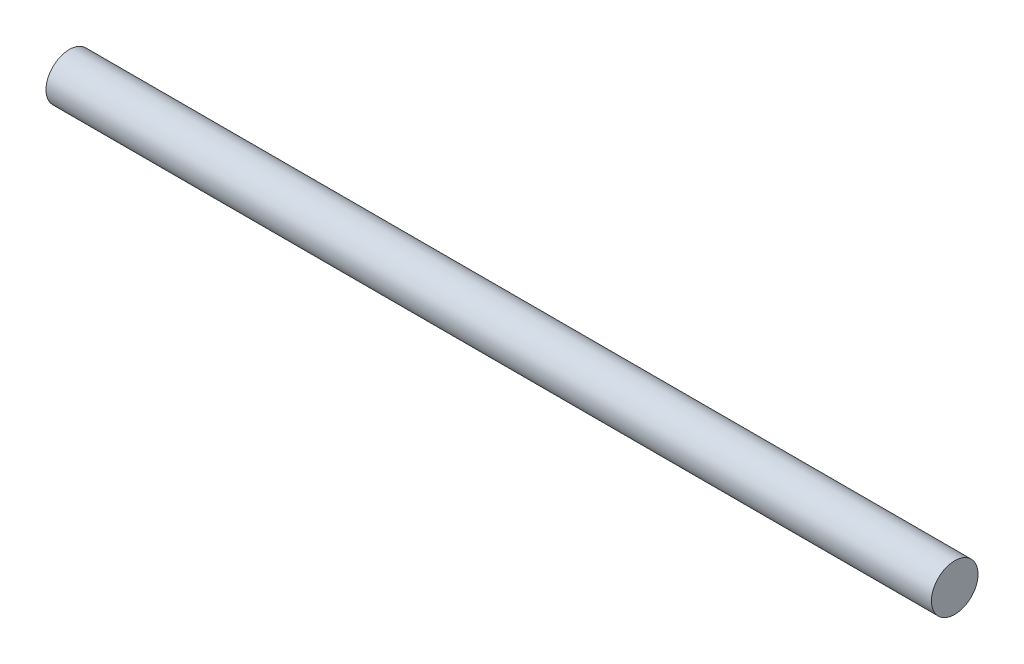
SolidWorks part; units mm, degrees
ref_plane "Front Plane" through (0, 0, 0) normal (0, 0, 1) x (1, 0, 0)
ref_plane "Top Plane" through (0, 0, 0) normal (0, 1, 0) x (1, 0, 0)
ref_plane "Right Plane" through (0, 0, 0) normal (1, 0, 0) x (0, 0, -1)
sketch "Sketch1" plane through (0, 0, 0) normal (1, 0, 0) x (0, 0, -1)
  circle A0 centre (0, 0) radius 2.54
  dimension "D1" = 5.08
extrude "Boss-Extrude1" add sketch "Sketch1" along normal blind 96.52
